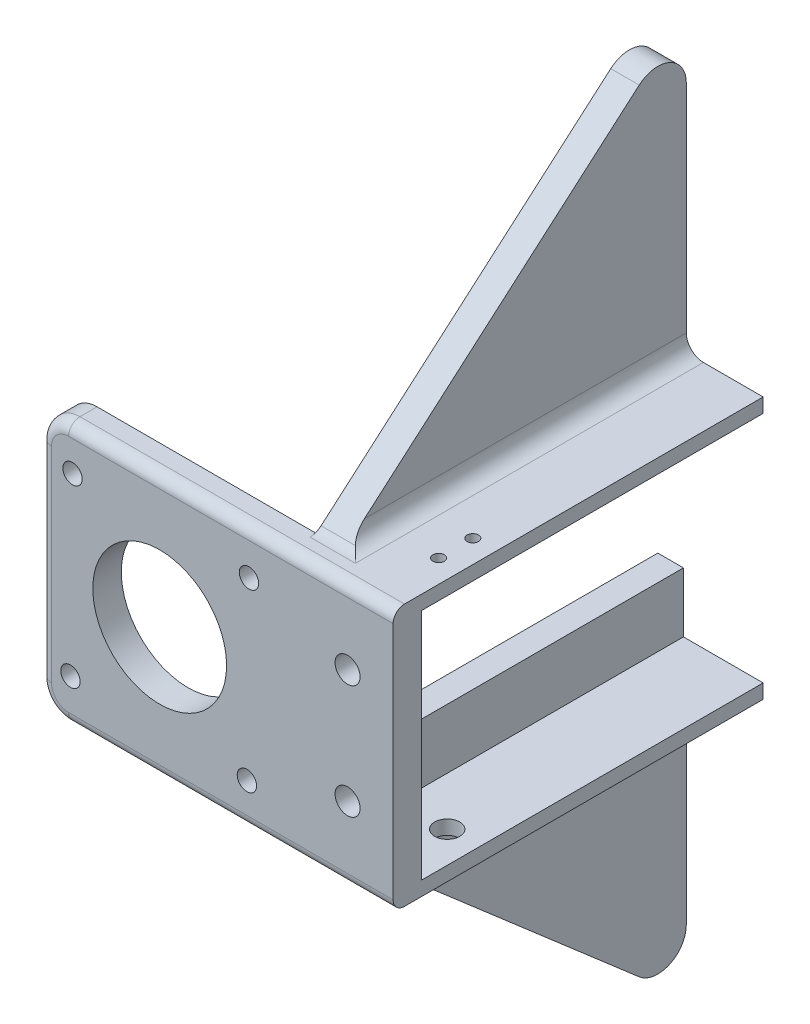
SolidWorks part; units mm, degrees
ref_plane "前视基准面" through (0, 0, 0) normal (0, 0, 1) x (1, 0, 0)
ref_plane "上视基准面" through (0, 0, 0) normal (0, 1, 0) x (1, 0, 0)
ref_plane "右视基准面" through (0, 0, 0) normal (1, 0, 0) x (0, 0, -1)
sketch "草图1" plane through (0, 0, 0) normal (0, 0, 1) x (1, 0, 0)
  line L0 (-21, 21.5) -> (-21, 23)
  line L1 (-21, -21.5) -> (21, -21.5)
  line L2 (-21, -21.5) -> (-21, 21.5)
  line L3 (-21, 21.5) -> (21, 21.5)
  line L4 (21, -21.5) -> (21, 21.5) construction
  line L5 (-21, -21.5) -> (21, 21.5) construction
  line L6 (-21, 21.5) -> (21, -21.5) construction
  line L7 (-21, 23) -> (22.5, 23)
  line L8 (22.5, 23) -> (22.5, -23)
  line L9 (22.5, -23) -> (-21, -23)
  line L10 (-21, -23) -> (-21, -21.5)
  line L11 (-1000, 0) -> (49000, 0) construction
  line L12 (22.5, 23) -> (27, 23)
  line L13 (27, 23) -> (41, 23)
  line L14 (41, 23) -> (41, -23)
  line L15 (41, -23) -> (27, -23)
  line L16 (27, -23) -> (22.5, -23)
  line L17 (27, -23) -> (27, 23)
  line L18 (27, 20.5) -> (41, 20.5)
  line L19 (27, -20.5) -> (41, -20.5)
  line L20 (21, 21.5) -> (22.5, 21.5)
  line L21 (21, -21.5) -> (22.5, -21.5)
  line L22 (27, 10) -> (22.5, 10)
  line L23 (27, -10) -> (22.5, -10)
  circle A0 centre (33, 10) radius 2.2
  circle A1 centre (33, -10) radius 2.2
  circle A2 centre (33, 10) radius 4 construction
  circle A3 centre (-15.3166, 15.6813) radius 1.7
  circle A4 centre (0, 0) radius 21.9203 construction
  circle A5 centre (0, 0) radius 11.75
  circle A6 centre (15.6813, 15.3166) radius 1.7
  circle A7 centre (15.3166, -15.6813) radius 1.7
  circle A8 centre (-15.6813, -15.3166) radius 1.7
  point P0 (0, 0)
  point P35 (0, 0)
  dimension "D7" = 4.4
  dimension "D9" = 8
  dimension "D10" = 6
  dimension "D11" = 23.5
  dimension "D14" = 3.4
  dimension "D1" = 42
  dimension "D2" = 43
  dimension "D3" = 46
  dimension "D4" = 43.5
  dimension "D5" = 4.5
  dimension "D6" = 14
  dimension "D8" = 20
  dimension "D12" = 4
  dimension "D13" = 31
  dimension "D15" = 41
  dimension "D16" = 20
  dimension "D17" = 2.5
extrude "凸台-拉伸1" add sketch "草图1" along normal blind 5 contours L17 L18 L14 L13 | L22 L17 L12 L8 | L3 L20 L8 L7 L0 | L1 L21 L8 L20 L3 L2 A8 A7 A6 A5 A3 | L17 L19 L14 L18 A0 A1 | L23 L17 L22 L8 | L17 L23 L8 L16 | L19 L17 L15 L14 | L21 L1 L10 L9 L8 region at (0, 20.8883, 0) region at (0.75, 22.25, 0) region at (0.75, -22.25, 0) region at (24.75, 16.5, 0) region at (34, 21.75, 0) region at (24.75, -16.5, 0) region at (24.75, 0, 0) region at (34.0559, 0, 0) region at (34, -21.75, 0)
extrude "凸台-拉伸2" add sketch "草图1<4>" against normal blind 60 contours L22 L17 L12 L8 | L17 L18 L14 L13 | L17 L23 L8 L16 | L19 L17 L15 L14 region at (24.75, 16.5, 0) region at (34, 21.75, 0) region at (24.75, -16.5, 0) region at (34, -21.75, 0)
sketch "草图1<4>" plane through (0, 0, 0) normal (0, 0, 1) x (1, 0, 0) same geometry as "草图1"
sketch "草图2" plane through (0, 0, 0) normal (0, 1, 0) x (1, 0, 0)
  line L1 (41, -5) -> (41, 60) construction
  line L2 (-981.7965, 10) -> (49018.2035, 10) construction
  circle A0 centre (35.5, 10) radius 2.2
  circle A1 centre (37, 13) radius 1
  circle A2 centre (37, 7) radius 1
  dimension "D2" = 4.4
  dimension "D6" = 2
  dimension "D1" = 10
  dimension "D3" = 5.5
  dimension "D4" = 4
  dimension "D5" = 6
extrude "切除-拉伸1" cut sketch "草图2" against normal up to next contours L2 A0 | A0 L2 region at (35.5, 0, -10.9337) region at (35.5, 0, -9.0663)
extrude "切除-拉伸2" cut sketch "草图2<3>" along normal up to next contours A2 | A1 region at (37, 0, -7)
sketch "草图2<3>" plane through (0, 0, 0) normal (0, 1, 0) x (1, 0, 0) same geometry as "草图2"
sketch "草图5" plane through (22.5, 0, 0) normal (-1, 0, 0) x (0, 0, 1)
  line L0 (-60, 23) -> (-60, 75)
  line L1 (-60, 75) -> (0, 23)
  line L2 (-60, 23) -> (0, 23) construction
  line L3 (-60, -23) -> (-60, -75)
  line L4 (-60, -75) -> (0, -23)
  line L5 (-60, -23) -> (0, -23) construction
  line L6 (0, 23) -> (-60, 23)
  line L7 (-60, 23) -> (-59.6174, 22.7315)
  line L8 (0, -23) -> (-60, -23)
  line L9 (-60, -23) -> (-59.6532, -23.735)
  line M2 (0, 23) -> (-60, 23)
  dimension "D1" = 60
  dimension "D2" = 150
  dimension "D3" = 75
extrude "凸台-拉伸3" add sketch "草图5" against normal blind 5 contours L1 L0 M2 | L4 L8 L3 region at (22.5, 40.3333, -40) region at (22.5, -40.3333, -40)
fillet "圆角1" radius 5 4 edges at (25, -75, -60) (25, 75, -60) (-21, -23, 2.5) (-21, 23, 2.5)
fillet "圆角2" radius 3 4 edges at (25, -23, 0)
fillet "圆角3" radius 2 5 edges at (12.5, -23, 5) (-19.5355, -21.5355, 5) (-21, 0, 5) (-19.5355, 21.5355, 5) (12.5, 23, 5)
